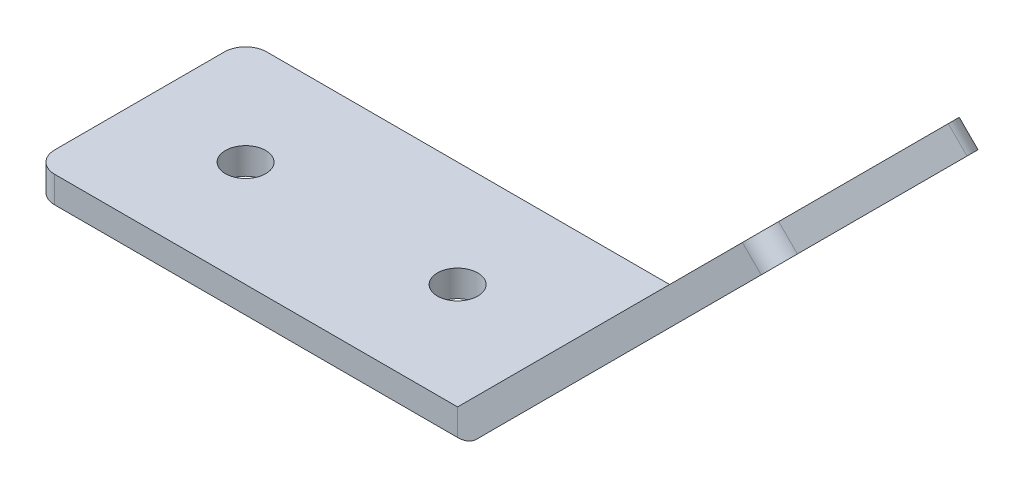
SolidWorks part; units mm, degrees
ref_plane "Front Plane" through (0, 0, 0) normal (0, 0, 1) x (1, 0, 0)
ref_plane "Top Plane" through (0, 0, 0) normal (0, 1, 0) x (1, 0, 0)
ref_plane "Right Plane" through (0, 0, 0) normal (1, 0, 0) x (0, 0, -1)
sketch "Sketch1" plane through (0, 0, 0) normal (0, 1, 0) x (1, 0, 0)
  line L1 (0, 0) -> (50.8, 0)
  line L2 (0, 0) -> (0, -25.4)
  line L3 (0, -25.4) -> (50.8, -25.4)
  line L4 (50.8, 0) -> (50.8, -25.4)
  dimension "D1" = 50.8
  dimension "D2" = 25.4
extrude "Boss-Extrude1" add sketch "Sketch1" along normal blind 3.175
sketch "Sketch2" plane through (0, 0, 25.4) normal (0, 0, 1) x (1, 0, 0)
  line L0 (50.8, 3.175) -> (86.721, 39.096)
  line L1 (0, 3.175) -> (50.8, 3.175) construction
  line L3 (53.0451, 0.9299) -> (88.9661, 36.851)
  line L4 (88.9661, 36.851) -> (86.721, 39.096)
  line L5 (0, 0) -> (50.8, 0) construction
  line L6 (50.8, 3.175) -> (50.8, 0)
  arc A0 (50.8, 0) -> (53.0451, 0.9299) centre (50.8, 3.175) ccw
  dimension "D1" = 50.8
  dimension "D2" = 135
  dimension "D3" = 3.175
  dimension "D4" = 135
extrude "Boss-Extrude2" add sketch "Sketch2" against normal up to surface (25.4 mm away) separate body up to face at (25.4, 1.5875, 0)
sketch "Sketch4" plane through (0, 3.175, 0) normal (0, 1, 0) x (1, 0, 0)
  line L0 (0, 0) -> (0, -25.4) construction
  line L1 (0, -12.7) -> (50.8, -12.7) construction
  line L2 (50.8, 0) -> (50.8, -25.4) construction
  circle A0 centre (38.1, -12.7) radius 2.413
  circle A1 centre (12.7, -12.7) radius 2.413
  dimension "D1" = 4.826
  dimension "D2" = 4.826
  dimension "D3" = 25.4
  dimension "D4" = 12.7
extrude "Cut-Extrude1" cut sketch "Sketch4" against normal up to surface (3.175 mm away) up to face at (25.4, 0, 12.7)
sketch "Sketch5" plane through (23.8125, -23.8125, 0) normal (-0.7071, 0.7071, 0) x (0, 0, 1)
  line L0 (12.7, 38.1661) -> (12.7, 88.9661) construction
  line L1 (25.4, 38.1661) -> (0, 38.1661) construction
  line L2 (0, 88.9661) -> (25.4, 88.9661) construction
  circle A0 centre (12.7, 50.8661) radius 2.413
  circle A1 centre (12.7, 76.2661) radius 2.413
  dimension "D1" = 4.826
  dimension "D2" = 4.826
  dimension "D3" = 25.4
  dimension "D4" = 12.7
extrude "Cut-Extrude2" cut sketch "Sketch5" against normal up to surface (3.175 mm away) up to face at (71.0056, 18.8904, 12.7)
fillet "Fillet1" radius 2.54 2 edges at (87.8436, 37.9735, 25.4) (87.8436, 37.9735, 0)
fillet "Fillet2" radius 2.54 2 edges at (0, 1.5875, 25.4) (0, 1.5875, 0)
